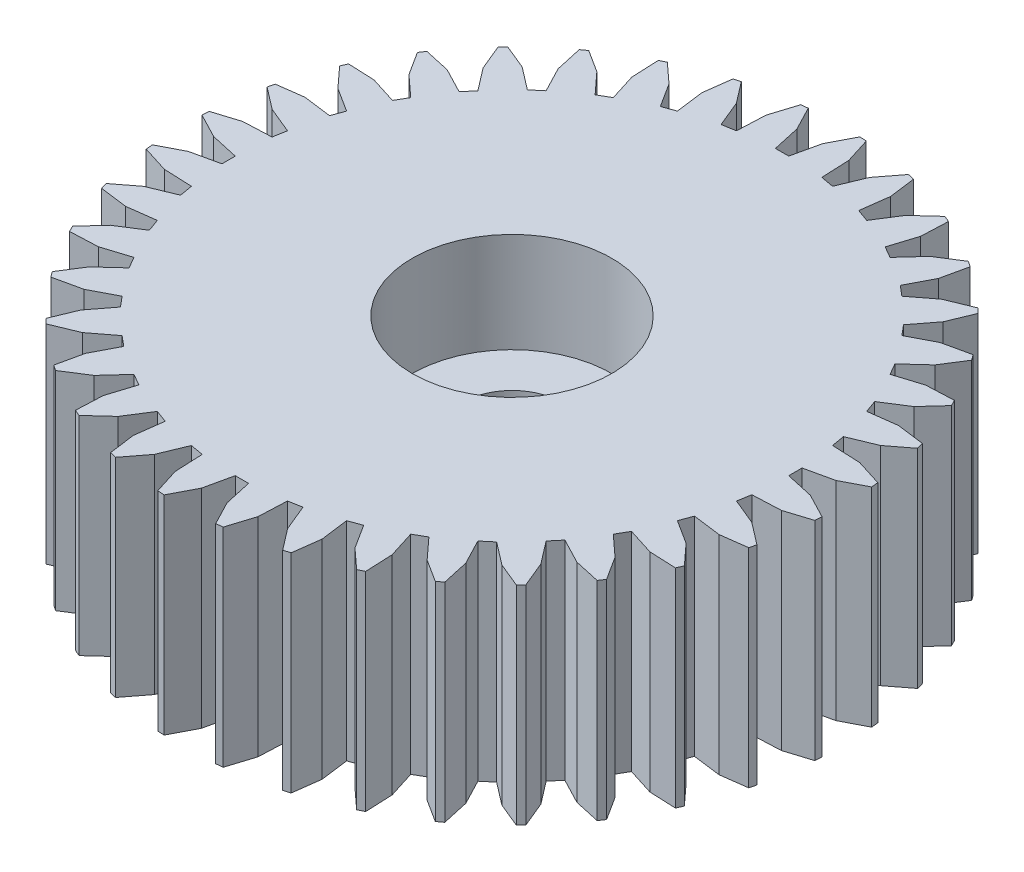
SolidWorks part; units mm, degrees
ref_plane "Front Plane" through (0, 0, 0) normal (0, 0, 1) x (1, 0, 0)
ref_plane "Top Plane" through (0, 0, 0) normal (0, 1, 0) x (1, 0, 0)
ref_plane "Right Plane" through (0, 0, 0) normal (1, 0, 0) x (0, 0, -1)
sketch "Sketch1" plane through (0, 0, 0) normal (0, 1, 0) x (1, 0, 0)
  circle A0 centre (0, 0) radius 10.0584
  dimension "D1" = 20.1168
extrude "Boss-Extrude1" add sketch "Sketch1" along normal blind 6.35
sketch "Sketch2" plane through (0, 6.35, 0) normal (0, 1, 0) x (1, 0, 0)
  circle A0 centre (0, 0) radius 1.524
  dimension "D1" = 3.048
extrude "Cut-Extrude1" cut sketch "Sketch2" against normal through all
sketch "Sketch3" plane through (0, 6.35, 0) normal (0, 1, 0) x (1, 0, 0)
  circle A0 centre (0, 0) radius 3.048
  dimension "D1" = 6.096
extrude "Cut-Extrude2" cut sketch "Sketch3" against normal blind 3.048
sketch "Sketch4" plane through (0, 0, 0) normal (0, -1, 0) x (1, 0, 0)
  line L0 (-0.9927, -10.0584) -> (-0.4064, -8.4474) construction
  line L1 (0, 0) -> (0, -10.0584) construction
  line L2 (-0.4064, -8.4474) -> (0, -8.4474)
  line L3 (0, -8.4474) -> (0.5863, -10.0584) construction
  line L4 (-0.9927, -10.0584) -> (-0.5935, -9.2915)
  line L5 (-0.5935, -9.2915) -> (-0.4064, -8.4474)
  line L6 (0, -8.4474) -> (0.1871, -9.2915)
  line L7 (0.1871, -9.2915) -> (0.5863, -10.0584)
  line L9 (0.5863, -10.0584) -> (0.9927, -10.0584) construction
  circle A0 centre (0, 0) radius 10.0584 construction
  dimension "D1" = 70
  dimension "D2" = 70
  dimension "D3" = 165
  dimension "D4" = 165
extrude "Cut-Extrude3" cut sketch "Sketch4" against normal through all flip side to cut
pattern_circular "CirPattern1" count 36 over 360 about axis through (0, 0, 0) along (0, 1, 0) of "Cut-Extrude3"
